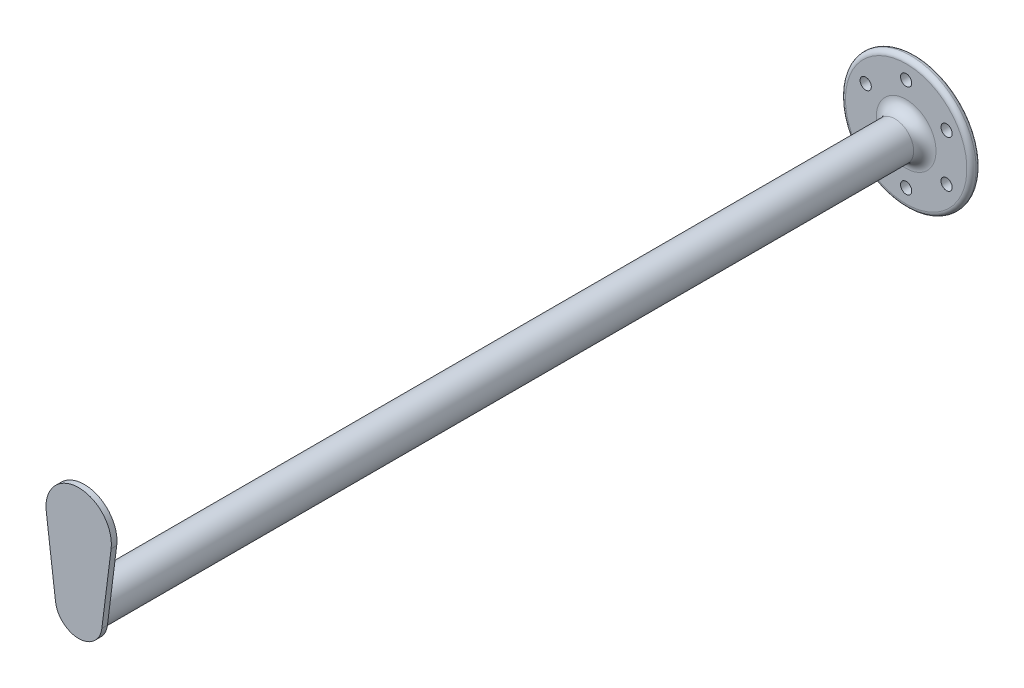
SolidWorks part; units mm, degrees
material "Alloy Steel"
ref_plane "Front" through (0, 0, 0) normal (0, 0, 1) x (1, 0, 0)
ref_plane "Top" through (0, 0, 0) normal (0, 1, 0) x (1, 0, 0)
ref_plane "Right" through (0, 0, 0) normal (1, 0, 0) x (0, 0, -1)
sketch "Sketch2" plane through (0, 0, 0) normal (0, 0, 1) x (1, 0, 0)
  circle A0 centre (0, 0) radius 12.7
  dimension "D1" = 25.4
extrude "Boss-Extrude1" add sketch "Sketch2" along normal blind 558.8
sketch "Sketch3" plane through (0, 0, 0) normal (0, 0, -1) x (-1, 0, 0)
  circle A0 centre (0, 0) radius 44.45
  circle A1 centre (0, 31.75) radius 3.81
  circle A2 centre (27.4963, 15.875) radius 3.81
  circle A3 centre (27.4963, -15.875) radius 3.81
  circle A4 centre (0, -31.75) radius 3.81
  circle A5 centre (-27.4963, -15.875) radius 3.81
  circle A6 centre (-27.4963, 15.875) radius 3.81
  point P18 (0, 0)
  dimension "D1" = 88.9
  dimension "D2" = 7.62
  dimension "D3" = 31.75
  dimension "D4" = 6
extrude "Boss-Extrude2" add sketch "Sketch3" along normal blind 6.35
fillet "Fillet1" radius 7.62 1 edges at (-12.7, 0, 0)
fillet "Fillet2" radius 3.175 2 edges at (-44.45, 0, -6.35) (-44.45, 0, 0)
sketch "Sketch4" plane through (0, 0, 558.8) normal (0, 0, 1) x (1, 0, 0)
  line L0 (-15.7505, -1.9844) -> (-22.0507, 48.0219)
  line L1 (15.7505, -1.9844) -> (22.0507, 48.0219)
  arc A0 (-15.7505, -1.9844) -> (15.7505, -1.9844) centre (0, 0) ccw
  arc A1 (22.0507, 48.0219) -> (-22.0507, 48.0219) centre (0, 50.8) ccw
  dimension "D1" = 31.75
  dimension "D2" = 44.45
  dimension "D3" = 50.8
extrude "Boss-Extrude3" add sketch "Sketch4" along normal blind 3.81
fillet "Fillet3" radius 1.27 1 edges at (12.7, 0, 558.8)
